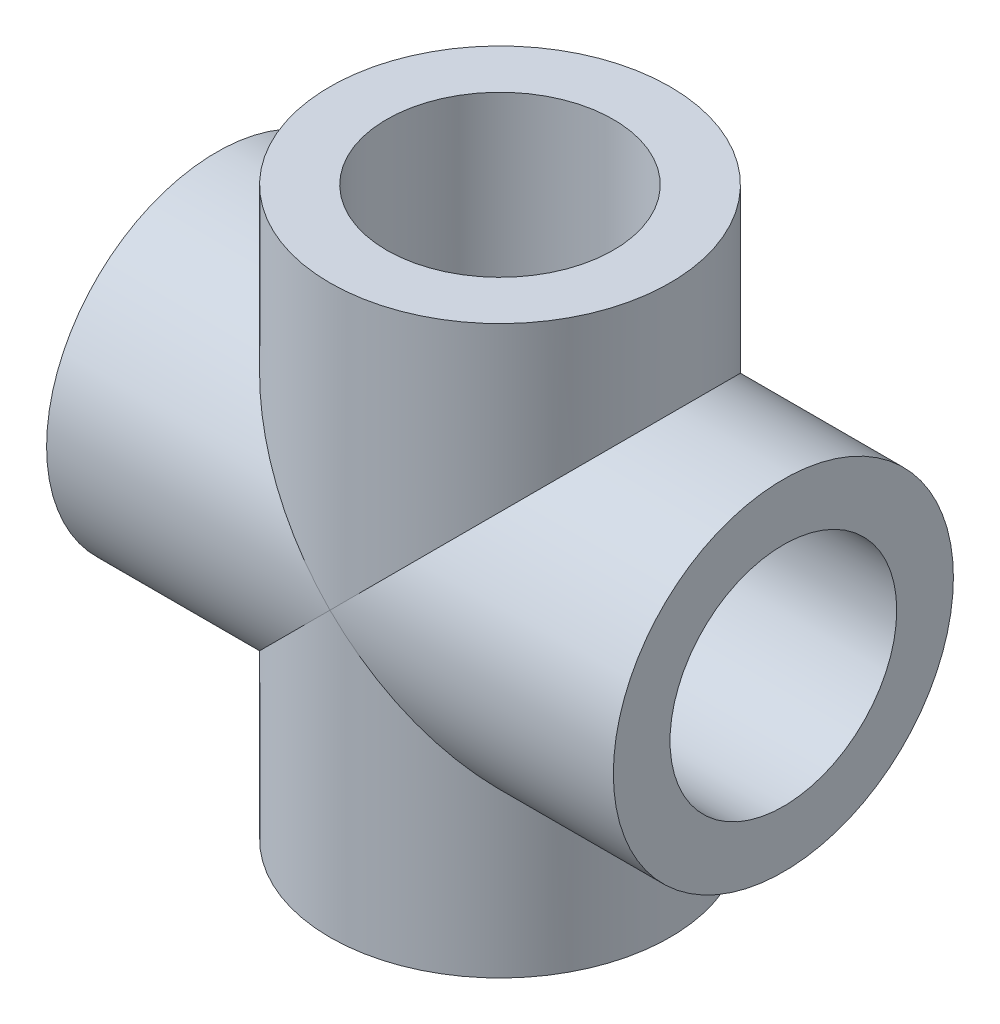
SolidWorks part; units mm, degrees
ref_plane "前视基准面" through (0, 0, 0) normal (0, 0, 1) x (1, 0, 0)
ref_plane "上视基准面" through (0, 0, 0) normal (0, 1, 0) x (1, 0, 0)
ref_plane "右视基准面" through (0, 0, 0) normal (1, 0, 0) x (0, 0, -1)
other "Configuration Table"
sketch "草图1" plane through (0, 0, 0) normal (0, 1, 0) x (1, 0, 0)
  circle A0 centre (0, 0) radius 15
  circle A1 centre (0, 0) radius 10
extrude "凸台-拉伸1" add sketch "草图1" along normal blind 50
sketch "草图3" plane through (0, 0, 0) normal (0, -1, 0) x (1, 0, 0)
  line L0 (0, 0) -> (19.5296, 0)
sketch "草图6" plane through (0, 0, 0) normal (0, -1, 0) x (1, 0, 0)
  line L0 (0, 0) -> (-15, 0)
  circle A0 centre (0, 0) radius 15 construction
sketch "草图9" plane through (0, 0, 0) normal (1, 0, 0) x (0, 0, -1)
  line L0 (0, 0) -> (0, 50)
  line L1 (10, 50) -> (-10, 50) construction
  circle A0 centre (0, 25) radius 15
extrude "凸台-拉伸6" add sketch "草图9" along normal blind 25 and the other way blind 25 contours L0 A0 | L0 A0 region at (0, 25, 6.3662) region at (0, 25, -6.3662)
sketch "草图10" plane through (0, 0, 0) normal (1, 0, 0) x (0, 0, -1)
  line L0 (0, 0) -> (0, 50)
  line L1 (15, 50) -> (-15, 50) construction
  circle A0 centre (0, 25) radius 10
extrude "切除-拉伸2" cut sketch "草图10" against normal blind 25 and the other way blind 25 contours L0 A0 | L0 A0 region at (0, 25, 4.2441) region at (0, 25, -4.2441)
sketch "草图11" plane through (0, 0, 0) normal (0, 1, 0) x (1, 0, 0)
  circle A0 centre (0, 0) radius 10
extrude "切除-拉伸3" cut sketch "草图11" against normal through all and the other way through all
